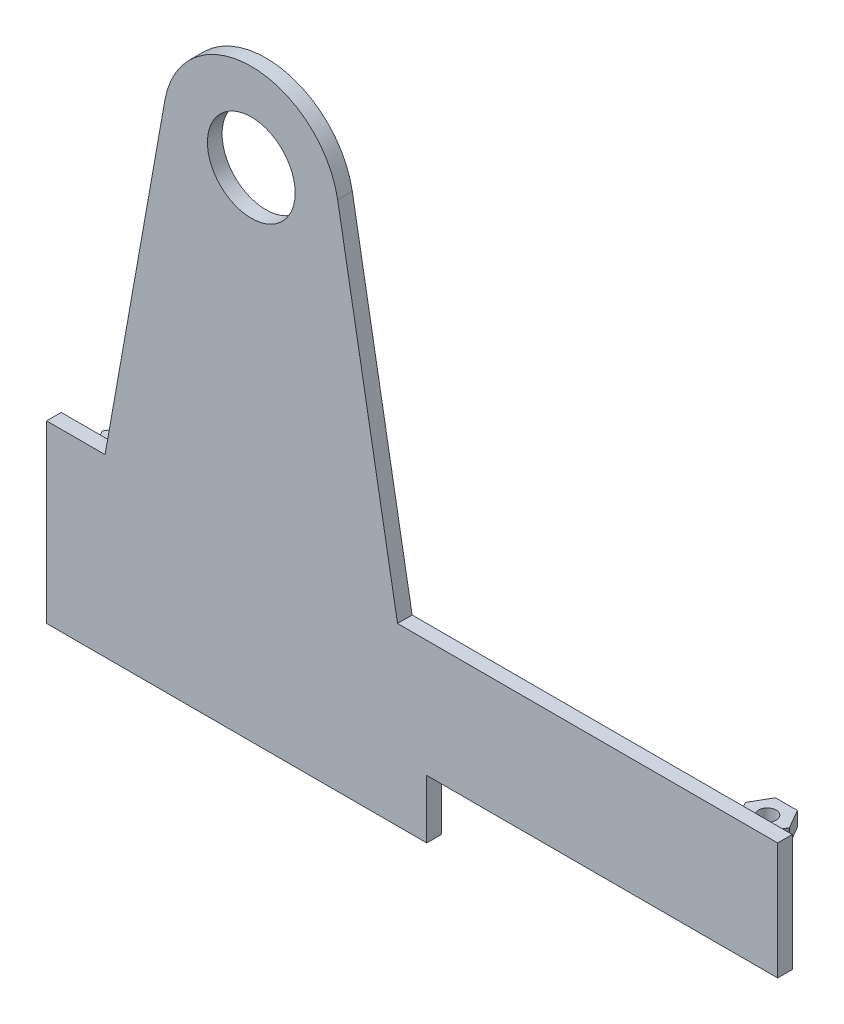
SolidWorks part; units mm, degrees
material "Сталь 3 ГОСТ 535-88"
ref_plane "Спереди" through (0, 0, 0) normal (0, 0, 1) x (1, 0, 0)
ref_plane "Сверху" through (0, 0, 0) normal (0, 1, 0) x (1, 0, 0)
ref_plane "Справа" through (0, 0, 0) normal (1, 0, 0) x (0, 0, -1)
sketch "Эскиз1" plane through (0, 0, 0) normal (0, 0, 1) x (1, 0, 0)
  line L0 (-65, 0) -> (-65, 60)
  line L1 (-65, 60) -> (185, 60)
  line L2 (185, 60) -> (185, 20)
  line L3 (185, 20) -> (65, 20)
  line L4 (65, 20) -> (65, 0)
  line L6 (65, 0) -> (-65, 0)
  dimension "D1" = 130
  dimension "D2" = 60
  dimension "D3" = 40
  dimension "D4" = 250
extrude "Бобышка-Вытянуть1" add sketch "Эскиз1" against normal blind 5
sketch "Эскиз2" plane through (0, 0, 0) normal (0, 0, 1) x (1, 0, 0)
  line L0 (-45, 60) -> (-24.538, 175.2446)
  line L1 (185, 60) -> (-65, 60) construction
  line L2 (34.538, 175.2446) -> (55, 60)
  line L3 (-45, 60) -> (55, 60)
  line L4 (5, 204.1229) -> (5, 138.6821) construction
  arc A0 (-24.538, 175.2446) -> (34.538, 175.2446) centre (5, 170) cw
  circle A1 centre (5, 170) radius 15
  point P12 (5, 60)
  dimension "D2" = 30
  dimension "D4" = 30
  dimension "D1" = 20
  dimension "D3" = 140
  dimension "D5" = 100
extrude "Бобышка-Вытянуть2" add sketch "Эскиз2" against normal up to surface (5 mm away) up to face at (61.6667, 26.6667, -5)
ref_plane "Плоскость1" through (0, 55, 0) normal (0, 1, 0) x (1, 0, 0)
sketch "Эскиз3" plane through (0, 55, 0) normal (0, 1, 0) x (1, 0, 0)
  line L0 (-65, 5) -> (65, 5) construction
  line L1 (162.4944, 11.5) -> (166.2472, 5)
  line L2 (166.2472, 5) -> (173.7528, 5)
  line L3 (173.7528, 5) -> (177.5056, 11.5)
  line L4 (177.5056, 11.5) -> (173.7528, 18)
  line L5 (173.7528, 18) -> (166.2472, 18)
  line L6 (166.2472, 18) -> (162.4944, 11.5)
  line L7 (185, 5) -> (185, 0) construction
  circle A0 centre (170, 11.5) radius 6.5 construction
  circle A1 centre (170, 11.5) radius 3
  dimension "D2" = 6
  dimension "D1" = 13
  dimension "D3" = 15
extrude "Бобышка-Вытянуть3" add sketch "Эскиз3" against normal blind 5 separate body
ref_plane "Плоскость2" through (60, 0, 0) normal (1, 0, 0) x (0, 0, -1)
mirror "Зеркальное отражение1" about plane through (60, 0, 0) normal (1, 0, 0) of bodies 105
